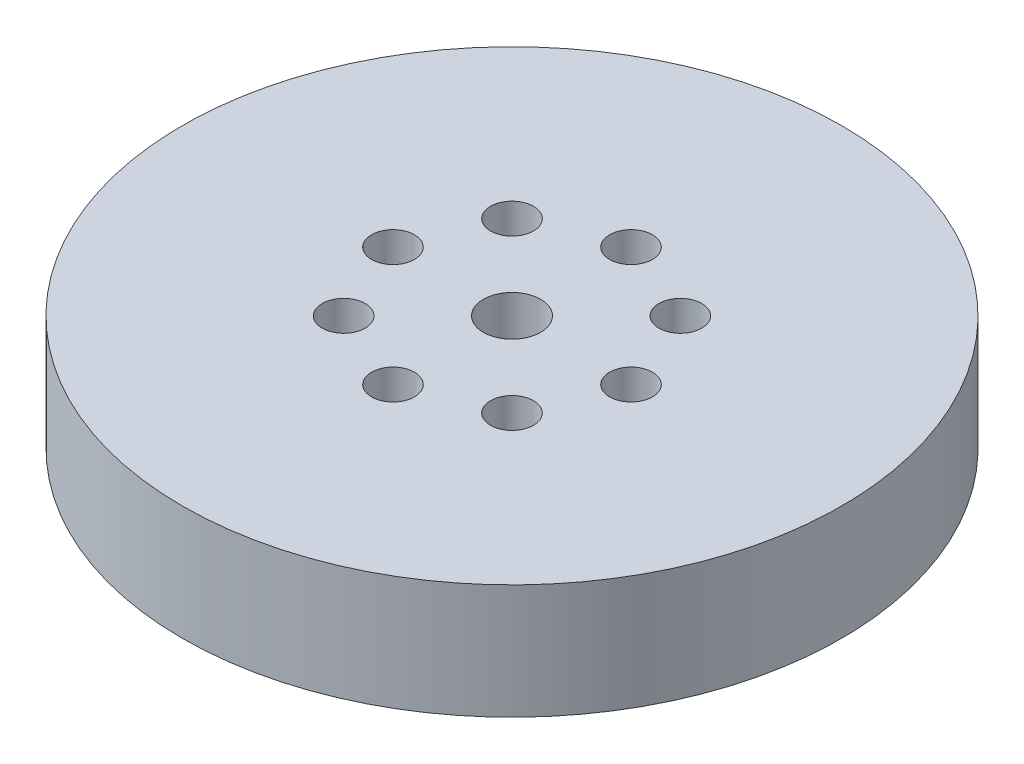
SolidWorks part; units mm, degrees
ref_plane "Front Plane" through (0, 0, 0) normal (0, 0, 1) x (1, 0, 0)
ref_plane "Top Plane" through (0, 0, 0) normal (0, 1, 0) x (1, 0, 0)
ref_plane "Right Plane" through (0, 0, 0) normal (1, 0, 0) x (0, 0, -1)
sketch "Sketch1" plane through (0, 0, 0) normal (0, 1, 0) x (1, 0, 0)
  circle A0 centre (0, 0) radius 57.5
  dimension "FLANGE_OD" = 115
extrude "Boss-Extrude1" add sketch "Sketch1" along normal blind 20
sketch "Sketch2" plane through (0, 0, 0) normal (0, 1, 0) x (1, 0, 0)
  circle A0 centre (0, 0) radius 5
  dimension "BORE_D" = 10
extrude "Cut-Extrude1" cut sketch "Sketch2" along normal through all
sketch "Sketch3" plane through (0, 20, 0) normal (0, 1, 0) x (1, 0, 0)
  circle A0 centre (0, 0) radius 20.7653 construction
  circle A1 centre (-20.7653, 0) radius 3.7397
  dimension "BOLT_D" = 7.4794
  dimension "BOLT_PCD" = 41.5305
extrude "Cut-Extrude2" cut sketch "Sketch3" against normal blind 19.0782
pattern_circular "CirPattern1" count 8 over 360 about axis through (0, 0, 0) along (0, 1, 0) of "Cut-Extrude2"
